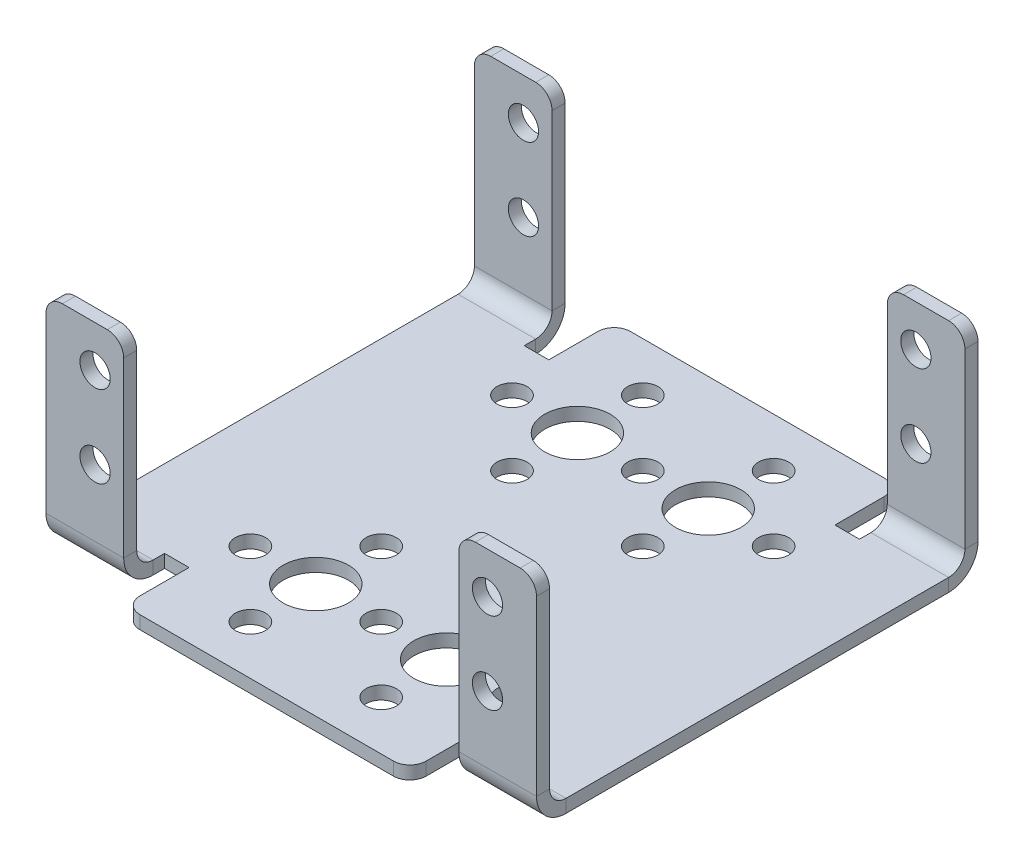
SolidWorks part; units mm, degrees
note: The reader was unsure of these and kept them because the rebuilt part matched: flange length of "Edge-Flange1".
other "Defeature"
material "5052-H34"
ref_plane "Front Plane" through (0, 0, 0) normal (0, 0, 1) x (1, 0, 0)
ref_plane "Top Plane" through (0, 0, 0) normal (0, 1, 0) x (1, 0, 0)
ref_plane "Right Plane" through (0, 0, 0) normal (1, 0, 0) x (0, 0, -1)
sketch "Sketch1" plane through (0, 0, 0) normal (0, 1, 0) x (1, 0, 0)
  line L0 (-30, 0) -> (30, 0)
  line L1 (30, -27) -> (30, 0)
  line L4 (30, -27) -> (20.5, -27)
  line L5 (20.5, -27) -> (20.5, -22)
  line L6 (20.5, -22) -> (17.5, -22)
  line L7 (17.5, -22) -> (17.5, -30)
  line L8 (17.5, -30) -> (-17.5, -30)
  line L9 (-17.5, -30) -> (-17.5, -22)
  line L10 (-17.5, -22) -> (-20.5, -22)
  line L11 (-20.5, -22) -> (-20.5, -27)
  line L12 (-20.5, -27) -> (-30, -27)
  line L13 (-30, -27) -> (-30, 0)
  point P0 (0, 0)
  dimension "D1" = 30
  dimension "D2" = 60
  dimension "D3" = 35
  dimension "D4" = 3
  dimension "D6" = 8
  dimension "D7" = 3
base flange "Base-Flange1" sketch "Sketch1" thickness 1.6 reverse thickness direction yes parameters "D1"=2
edge flange "Edge-Flange1" sketch "Sketch13" flange profiles "Sketch13", "Sketch14" flange angle 90 flange length 26.8 flange position material inside bend radius 2 thickness 1.6 relief rectangular parameters "D6"=10, "D8"=1
sketch "Sketch13" plane through (0, 1.6, 27) normal (0, 0, 1) x (1, 0, 0)
  line L0 (20.5, 0) -> (30, 0) construction
  line L1 (20.5, 0) -> (30, 0)
  line L2 (20.5, 0) -> (20.5, 25.2)
  line L3 (20.5, 25.2) -> (30, 25.2)
  line L4 (30, 25.2) -> (30, 0)
sketch "Sketch14" plane through (0, 1.6, 27) normal (0, 0, 1) x (1, 0, 0)
  line L0 (-30, 0) -> (-20.5, 0) construction
  line L1 (-30, 0) -> (-20.5, 0)
  line L2 (-30, 0) -> (-30, 25.2)
  line L3 (-30, 25.2) -> (-20.5, 25.2)
  line L4 (-20.5, 25.2) -> (-20.5, 0)
bend "EdgeBend2" bend radius 2 bend angle 90 parameters "D5"=2
bend "EdgeBend3" bend radius 2 bend angle 90 parameters "D5"=3
sketch "Sketch15" plane through (0, 1.6, 0) normal (0, 1, 0) x (1, 0, 0)
  line L0 (30, 0) -> (-30, 0) construction
  circle A0 centre (0, -16) radius 1.85
  circle A1 centre (8, -16) radius 4
  circle A2 centre (-8, -16) radius 4
  circle A3 centre (16, -16) radius 1.85
  circle A4 centre (-16, -16) radius 1.85
  circle A5 centre (-8, -8) radius 1.85
  circle A6 centre (-8, -24) radius 1.85
  circle A7 centre (8, -24) radius 1.85
  circle A8 centre (8, -8) radius 1.85
  circle A9 centre (8, -16) radius 8 construction
  circle A10 centre (-8, -16) radius 8 construction
  dimension "D1" = 3.7
  dimension "D2" = 8
  dimension "D3" = 16
  dimension "D4" = 16
extrude "Cut-Extrude1" cut sketch "Sketch15" against normal up to next normal cut yes
sketch "Sketch16" plane through (0, 0, 27) normal (0, 0, 1) x (1, 0, 0)
  line L0 (0, 0) -> (0, 26.8) construction
  line L3 (-20.5, 26.8) -> (-30, 26.8) construction
  circle A0 centre (-24, 21.75) radius 1.85
  circle A1 centre (-24, 11.75) radius 1.85
  circle A2 centre (24, 21.75) radius 1.85
  circle A3 centre (24, 11.75) radius 1.85
  point P13 (-22.15, 21.75)
  point P14 (-24, 23.6)
  dimension "D1" = 3.7
  dimension "D2" = 48
  dimension "D3" = 3.2
  dimension "D4" = 10
extrude "Cut-Extrude2" cut sketch "Sketch16" against normal up to next normal cut yes
fillet "Fillet1" radius 2 6 edges at (30, 26.8, 26.2) (20.5, 26.8, 26.2) (-20.5, 26.8, 26.2) (-30, 26.8, 26.2) (17.5, 0.8, 30) (-17.5, 0.8, 30)
mirror "Mirror1" about plane through (-30, 1.6, 0) normal (0, 0, 1) of bodies 104
bend "MirrorBend1" bend radius 2 bend angle 90 parameters "D5"=4
bend "MirrorBend2" bend radius 2 bend angle 90 parameters "D5"=5
sketch "Bend-Lines1" [suppressed] plane through (0, 0, 0) normal (0, 1, 0) x (-1, 0, 0)
sketch "Bounding-Box1" [suppressed] plane through (0, 0, 0) normal (0, 1, 0) x (-1, 0, 0)
sheet metal parameters "Sheet-Metal1" thickness 1.6 parameters "D1"=2
flat pattern "Flat-Pattern1" [suppressed]
sketch "Bend-Lines2" plane through (0, 0, 0) normal (0, 1, 0) x (-1, 0, 0)
sketch "Bounding-Box2" [suppressed] plane through (0, 0, 0) normal (0, 1, 0) x (-1, 0, 0)
sheet metal parameters "Sheet-Metal2" thickness 1.6 parameters "D1"=2
flat pattern "Flat-Pattern1" [suppressed]
sketch "Bend-Lines2" plane through (0, 0, 0) normal (0, 1, 0) x (-1, 0, 0)
sketch "Bounding-Box2" [suppressed] plane through (0, 0, 0) normal (0, 1, 0) x (-1, 0, 0)
bend of the flat pattern "Flatten-<EdgeBend2>1"
bend of the flat pattern "Flatten-<EdgeBend3>1"
sheet metal parameters "Sheet-Metal3" thickness 1.6 parameters "D1"=2
flat pattern "Flat-Pattern1" [suppressed]
sketch "Bend-Lines2" plane through (0, 0, 0) normal (0, 1, 0) x (-1, 0, 0)
sketch "Bounding-Box2" [suppressed] plane through (0, 0, 0) normal (0, 1, 0) x (-1, 0, 0)
bend of the flat pattern "Flatten-<EdgeBend2>1"
bend of the flat pattern "Flatten-<EdgeBend3>1"
sheet metal parameters "Sheet-Metal4" thickness 1.6 parameters "D1"=2
flat pattern "Flat-Pattern1" [suppressed]
sketch "Bend-Lines2" plane through (0, 0, 0) normal (0, 1, 0) x (-1, 0, 0)
sketch "Bounding-Box2" [suppressed] plane through (0, 0, 0) normal (0, 1, 0) x (-1, 0, 0)
bend of the flat pattern "Flatten-<EdgeBend2>1"
bend of the flat pattern "Flatten-<EdgeBend3>1"
sheet metal parameters "Sheet-Metal6" thickness 1.6 parameters "D1"=2
flat pattern "Flat-Pattern6"
sketch "Bend-Lines3" plane through (0, 0, 0) normal (0, -1, 0) x (-1, 0, 0)
  line L0 (30, 25.5991) -> (20.5, 25.5991) construction
  line L1 (-20.5, 25.5991) -> (-30, 25.5991) construction
  line L2 (20.5, -25.5991) -> (30, -25.5991) construction
  line L3 (-30, -25.5991) -> (-20.5, -25.5991) construction
  line L4 (30, 25.5991) -> (20.5, 25.5991) construction
  line L5 (-20.5, 25.5991) -> (-30, 25.5991) construction
  line L6 (20.5, -25.5991) -> (30, -25.5991) construction
  line L7 (-30, -25.5991) -> (-20.5, -25.5991) construction
sketch3d "Bounding-Box3" [suppressed]
  line L0 (-30.0001, -50.9982, 0) -> (-30, 50.9982, 0) construction
  line L1 (29.9999, -50.9982, 0) -> (30, 50.9982, 0) construction
  line L2 (-30.0001, -50.9982, 0) -> (29.9999, -50.9982, 0) construction
  line L3 (-30, 50.9982, 0) -> (30, 50.9982, 0) construction
bend of the flat pattern "Flatten-<EdgeBend2>2"
bend of the flat pattern "Flatten-<EdgeBend3>2"
bend of the flat pattern "Flatten-<MirrorBend1>1"
bend of the flat pattern "Flatten-<MirrorBend2>1"
